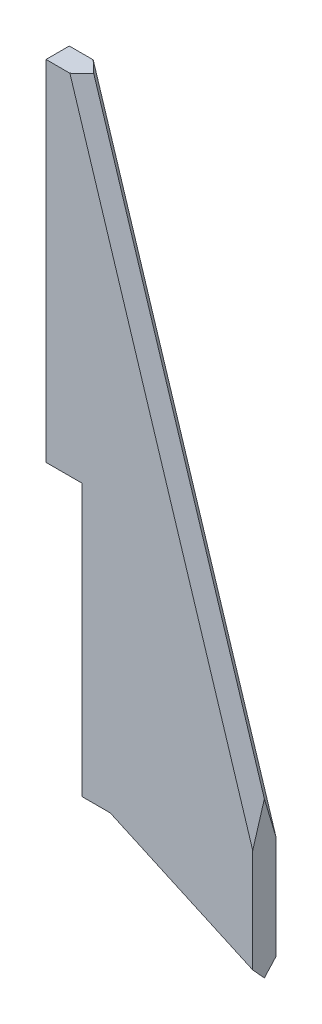
SolidWorks part; units mm, degrees
material "Pine"
ref_plane "Front Plane" through (0, 0, 0) normal (0, 0, 1) x (1, 0, 0)
ref_plane "Top Plane" through (0, 0, 0) normal (0, 1, 0) x (1, 0, 0)
ref_plane "Right Plane" through (0, 0, 0) normal (1, 0, 0) x (0, 0, -1)
sketch "Sketch1" plane through (0, 0, 0) normal (0, 0, 1) x (1, 0, 0)
  line L0 (0, 0) -> (0, 80)
  line L1 (0, 80) -> (22, 10)
  line L2 (22, 10) -> (22, -10)
  line L3 (22, -10) -> (0, 0)
  dimension "D1" = 80
  dimension "D2" = 22
  dimension "D3" = 70
  dimension "D4" = 20
extrude "Boss-Extrude1" add sketch "Sketch1" along normal mid plane 3
sketch "Sketch7" plane through (0, 0, 0) normal (-1, 0, 0) x (0, 0, 1)
  line L4 (-1.5, 80) -> (-1.5, 0)
  line L5 (-1.5, 0) -> (1.5, 0)
  line L6 (1.5, 0) -> (1.5, 80)
  line L7 (1.5, 80) -> (-1.5, 80)
  line L8 (-1.5, 80) -> (-1.5, 0)
  line L9 (-1.5, 0) -> (1.5, 0)
  line L10 (1.5, 0) -> (1.5, 80)
  line L11 (1.5, 80) -> (-1.5, 80)
  dimension "D1" = 0
extrude "Boss-Extrude2" add sketch "Sketch7" along normal blind 4.655
chamfer "Chamfer1" distance 1.5 angle 45 4 edges at (11, -5, 1.5) (11, -5, -1.5) (11, 45, -1.5) (11, 45, 1.5)
sketch "Sketch8" plane through (0, 0, 0) normal (0, 0, 1) x (1, 0, 0)
  line L1 (-4.655, 0) -> (0, 0)
  line L2 (-4.655, 0) -> (-4.655, 35)
  line L3 (-4.655, 35) -> (0, 35)
  line L4 (0, 0) -> (0, 35)
  line L6 (-4.655, 0) -> (3.6249, 0)
  line L7 (3.6249, 0) -> (22, -8.3523)
  line L8 (22, -8.3523) -> (22, 4.9971)
  line L9 (22, 4.9971) -> (-1.5723, 80)
  line L10 (-1.5723, 80) -> (-4.655, 80)
  line L11 (-4.655, 80) -> (-4.655, 0)
  line L12 (-4.655, 0) -> (3.6249, 0) construction
  line L13 (3.6249, 0) -> (22, -8.3523) construction
  line L14 (22, -8.3523) -> (22, 4.9971) construction
  line L15 (22, 4.9971) -> (-1.5723, 80) construction
  line L16 (-1.5723, 80) -> (-4.655, 80) construction
  line L17 (-4.655, 80) -> (-4.655, 0) construction
  dimension "D2" = 35
  dimension "D3" = 4.655
  dimension "D1" = 0
extrude "Cut-Extrude1" cut sketch "Sketch8" against normal through all both and the other way through all
